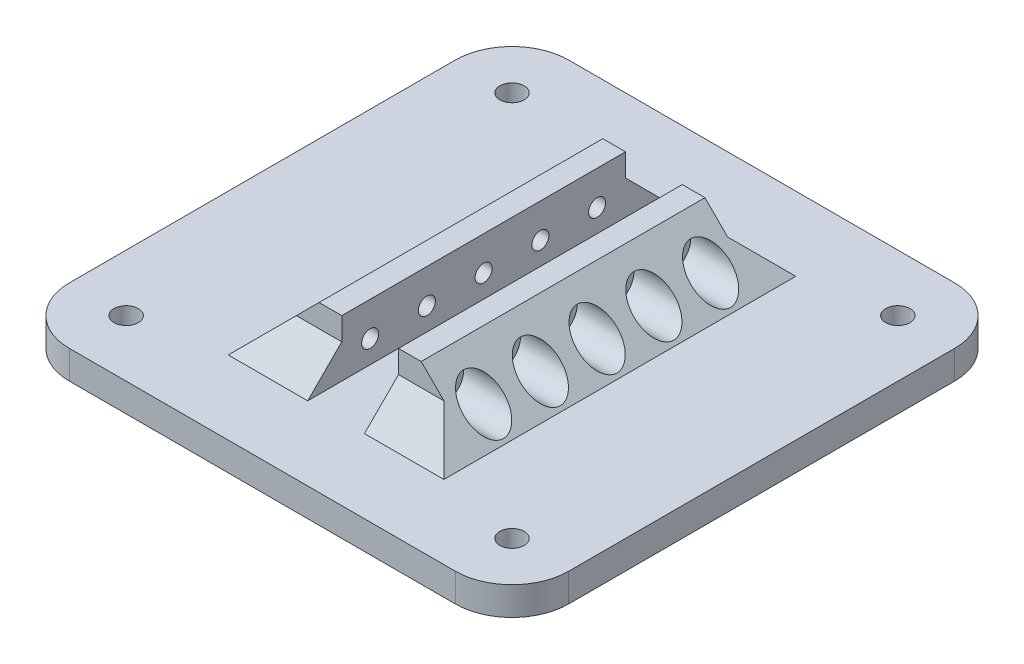
SolidWorks part; units mm, degrees
ref_plane "Front Plane" through (0, 0, 0) normal (0, 0, 1) x (1, 0, 0)
ref_plane "Top Plane" through (0, 0, 0) normal (0, 1, 0) x (1, 0, 0)
ref_plane "Right Plane" through (0, 0, 0) normal (1, 0, 0) x (0, 0, -1)
sketch "Sketch1" plane through (0, 0, 0) normal (0, 1, 0) x (1, 0, 0)
  line L1 (44, -44) -> (-44, -44)
  line L2 (44, -44) -> (44, 44)
  line L3 (44, 44) -> (-44, 44)
  line L4 (-44, -44) -> (-44, 44)
  line L5 (44, -44) -> (-44, 44) construction
  line L6 (44, 44) -> (-44, -44) construction
  point P0 (0, 0)
  dimension "D1" = 88
extrude "Boss-Extrude1" add sketch "Sketch1" along normal blind 5
fillet "Fillet1" radius 10 4 edges at (-44, 2.5, -44) (44, 2.5, -44) (-44, 2.5, 44) (44, 2.5, 44)
sketch "Sketch2" plane through (0, 5, 0) normal (0, 1, 0) x (1, 0, 0)
  circle A0 centre (34, 34) radius 2.15
  circle A1 centre (34, -34) radius 2.15
  circle A2 centre (-34, -34) radius 2.15
  circle A3 centre (-34, 34) radius 2.15
  dimension "D1" = 4.3
extrude "Cut-Extrude1" cut sketch "Sketch2" against normal through all
sketch "Sketch3" plane through (0, 5, 0) normal (0, 1, 0) x (1, 0, 0)
  line L0 (0, -1000) -> (0, 49000) construction
  line L1 (-9, -25) -> (-5, -25)
  line L2 (-9, -25) -> (-9, 25)
  line L3 (-9, 25) -> (-5, 25)
  line L4 (-5, -25) -> (-5, 25)
  line L5 (-9, -25) -> (-5, 25) construction
  line L6 (-9, 25) -> (-5, -25) construction
  line L7 (5, -25) -> (9, -25)
  line L8 (5, -25) -> (5, 25)
  line L9 (5, 25) -> (9, 25)
  line L10 (9, -25) -> (9, 25)
  line L11 (5, -25) -> (9, 25) construction
  line L12 (5, 25) -> (9, -25) construction
  point P0 (-7, 0)
  point P5 (7, 0)
  dimension "D1" = 10
  dimension "D2" = 4
  dimension "D4" = 50
extrude "Boss-Extrude2" add sketch "Sketch3" along normal blind 10
chamfer "Chamfer1" distance 10 angle 45 2 edges at (9, 5, 0) (-9, 5, 0)
sketch "Sketch4" plane through (0, 0, 0) normal (1, 0, 0) x (0, 0, -1)
  line L0 (-25, 5) -> (-25, 15) construction
  line L1 (-34, 5) -> (34, 5) construction
  circle A0 centre (-20, 9) radius 1.5
  dimension "D1" = 3
  dimension "D2" = 5
  dimension "D3" = 4
extrude "Cut-Extrude2" cut sketch "Sketch4" against normal through all and the other way through all
sketch "Sketch5" plane through (44, 0, 0) normal (1, 0, 0) x (0, 0, -1)
  circle A0 centre (-20, 9) radius 3.5
  dimension "D1" = 7
extrude "Cut-Extrude3" cut sketch "Sketch5" against normal offset from surface (36 mm away) 3 up to face at (5, 9, 18.5)
sketch "Sketch6" plane through (-44, 0, 0) normal (-1, 0, 0) x (0, 0, 1)
  circle A0 centre (20, 9) radius 3.5
  dimension "D1" = 7
extrude "Cut-Extrude4" cut sketch "Sketch6" against normal offset from surface (36 mm away) 3 up to face at (-5, 9, 21.5)
pattern_linear "LPattern2" count 5 spacing 10 along (0, 0, -1) of "Cut-Extrude2", "Cut-Extrude3", "Cut-Extrude4"
chamfer "Chamfer2" distance 6 angle 45 4 edges at (-12, 5, 25) (-12, 5, -25) (12, 5, -25) (12, 5, 25)
